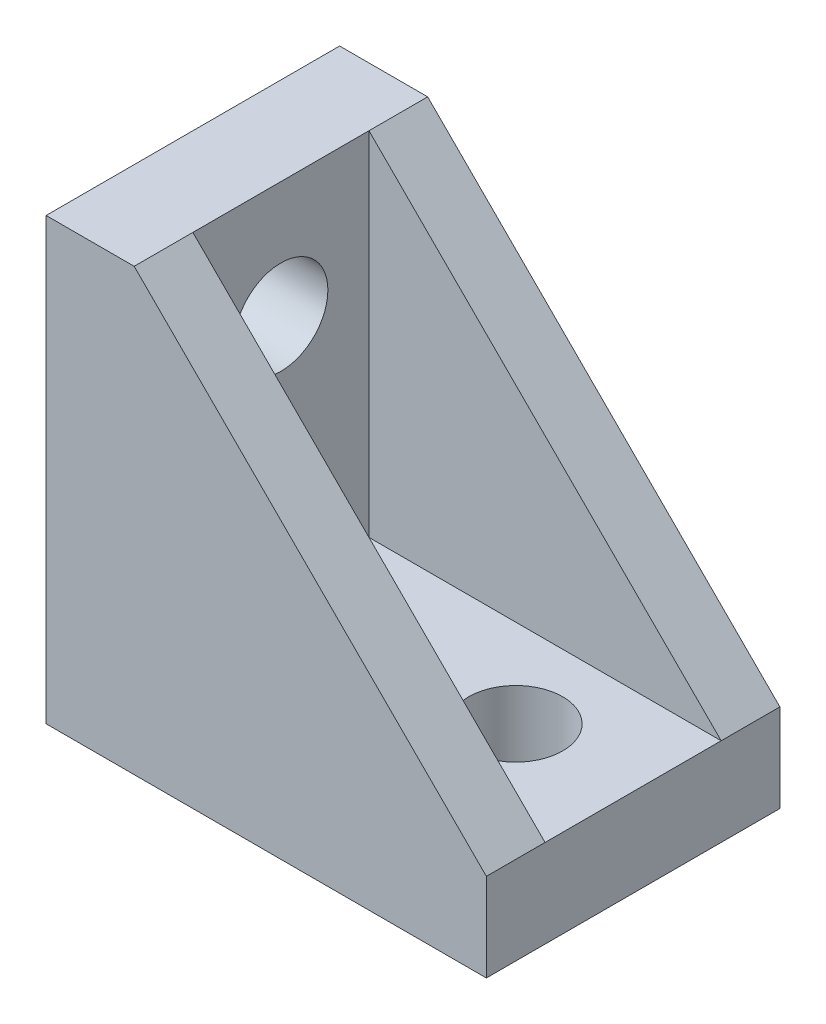
SolidWorks part; units mm, degrees
ref_plane "Front Plane" through (0, 0, 0) normal (0, 0, 1) x (1, 0, 0)
ref_plane "Top Plane" through (0, 0, 0) normal (0, 1, 0) x (1, 0, 0)
ref_plane "Right Plane" through (0, 0, 0) normal (1, 0, 0) x (0, 0, -1)
sketch "Sketch1" plane through (0, 0, 0) normal (0, 0, 1) x (1, 0, 0)
  line L0 (0, 0) -> (0, 15)
  line L1 (0, 15) -> (3, 15)
  line L2 (3, 15) -> (15, 3)
  line L3 (15, 3) -> (15, 0)
  line L4 (15, 0) -> (0, 0)
  line L5 (0, 11) -> (7, 11) construction
  line L6 (3, 15) -> (3, 3)
  line L7 (3, 3) -> (15, 3)
  dimension "D1" = 3
  dimension "D2" = 3
  dimension "D3" = 11
  dimension "D4" = 15
  dimension "D5" = 45
extrude "Boss-Extrude1" add sketch "Sketch1" along normal blind 3 contours L5 L0 L4 L3 L7 L6 | L0 L5 L6 L1 region at (0.186, 5.5, 0) region at (1.5, 13, 0)
extrude "Boss-Extrude3" add sketch "Sketch1<4>" against normal blind 2 contours L0 L5 L6 L1 | L5 L6 L7 L2 | L5 L0 L4 L3 L7 L6 | L6 L5 L2 region at (0.186, 5.5, 0) region at (1.5, 13, 0) region at (4.3333, 12.3333, 0) region at (7.3333, 6.3333, 0)
sketch "Sketch1<4>" plane through (0, 0, 0) normal (0, 0, 1) x (1, 0, 0) same geometry as "Sketch1"
mirror "Mirror1" about plane through (0, 0, 3) normal (0, 0, 1) of bodies 102
sketch "Sketch2" plane through (3, 0, 0) normal (1, 0, 0) x (0, 0, -1)
  line L0 (-3, 0) -> (-3, 11) construction
  line L1 (-8, 0) -> (2, 0) construction
  circle A0 centre (-3, 11) radius 1.6
  dimension "D2" = 3.2
  dimension "D1" = 11
extrude "Cut-Extrude1" cut sketch "Sketch2" against normal through all
ref_plane "Plane1" through (0, 0, 0) normal (0.7071, -0.7071, 0) x (0, 0, -1)
mirror "Mirror2" about plane through (0, 0, 0) normal (0.7071, -0.7071, 0) of "Cut-Extrude1"
